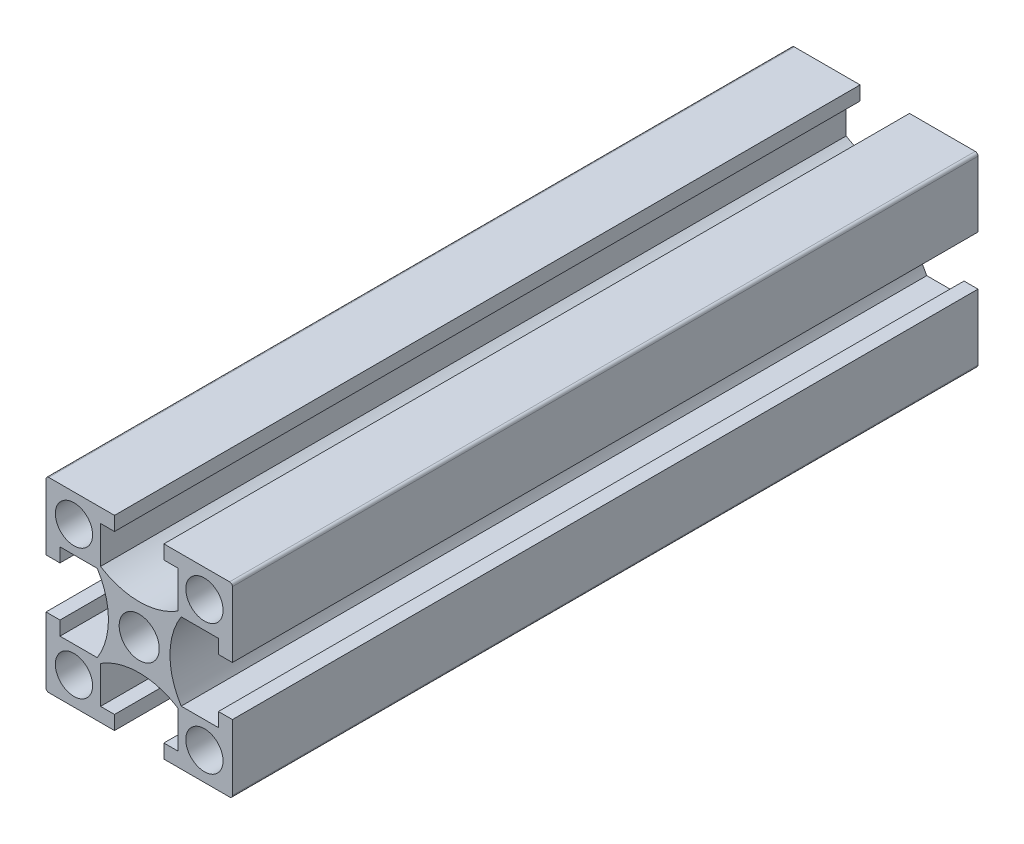
SolidWorks part; units mm, degrees
ref_plane "정면" through (0, 0, 0) normal (0, 0, 1) x (1, 0, 0)
ref_plane "윗면" through (0, 0, 0) normal (0, 1, 0) x (1, 0, 0)
ref_plane "우측면" through (0, 0, 0) normal (1, 0, 0) x (0, 0, -1)
sketch "스케치1" plane through (0, 0, 0) normal (0, 0, 1) x (1, 0, 0)
  line L0 (0, 32.0265) -> (0, -31.6588) construction
  line L1 (-10, 10) -> (-10, -10)
  line L2 (-10, 10) -> (10, 10)
  line L3 (-10, 2.65) -> (-8.5, 2.65)
  line L4 (13.6618, 0) -> (-11.6993, 0) construction
  line L5 (-8.5, 2.65) -> (-8.5, 4.15)
  line L6 (-8.5, 4.15) -> (-4.5032, 4.15)
  line L7 (-10, -2.65) -> (-8.5, -2.65)
  line L8 (-8.5, -2.65) -> (-8.5, -4.15)
  line L9 (-8.5, -4.15) -> (-4.5032, -4.15)
  line L10 (-10, -10) -> (10, -10)
  line L11 (10, 10) -> (10, -10)
  circle A0 centre (-7, 7) radius 2
  circle A1 centre (-7, -7) radius 2
  arc A2 (-4.5032, 4.15) -> (-4.5032, -4.15) centre (-11.0587, 0) cw
  circle A3 centre (0, 0) radius 2.15
  circle A4 centre (7, 7) radius 2
  circle A5 centre (7, -7) radius 2
  point P21 (-10, 0)
  point P23 (-3.3, 0)
  point P31 (0, -10)
  point P32 (0, 10)
  dimension "D3" = 4
  dimension "D9" = 6.7
  dimension "D10" = 4.3
  dimension "D11" = 7.7587
  dimension "D1" = 20
  dimension "D2" = 20
  dimension "D4" = 14
  dimension "D5" = 14
  dimension "D6" = 5.3
  dimension "D7" = 8.3
  dimension "D8" = 1.5
extrude "보스-돌출1" add sketch "스케치1" along normal blind 80 contours A0 | A4 | A3 | A5 | A1 | A2 L6 L5 L3 L1 L7 L8 L9 | L2 L11 L10 L1 region at (-6.6069, 0, 0) region at (-7, 7, 0) region at (-7, -7, 0) region at (0, 0, 0) region at (7, 7, 0) region at (7, -7, 0)
extrude "컷-돌출1" cut sketch "스케치1<3>" along normal up to next contours A2 L6 L5 L3 L1 L7 L8 L9 region at (-6.6069, 0, 0)
sketch "스케치1<3>" plane through (0, 0, 0) normal (0, 0, 1) x (1, 0, 0) same geometry as "스케치1"
pattern_circular "원형 패턴1" count 4 over 360 about axis through (0, 0, 80) along (0, 0, -1) of "컷-돌출1" reverse direction yes
fillet "필렛1" radius 0.3 4 edges at (10, -10, 40) (-10, -10, 40) (-10, 10, 40) (10, 10, 40)
